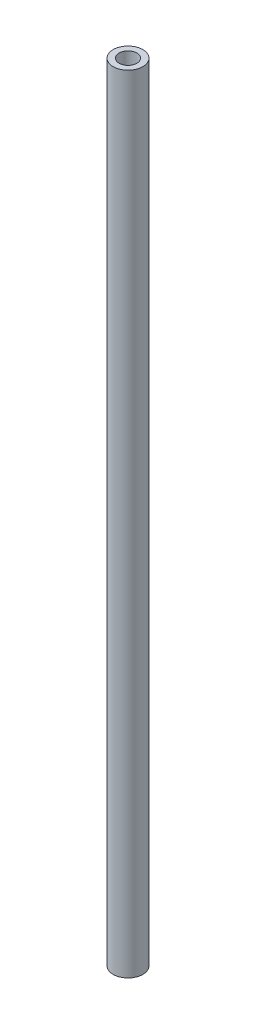
SolidWorks part; units mm, degrees
ref_plane "Front Plane" through (0, 0, 0) normal (0, 0, 1) x (1, 0, 0)
ref_plane "Top Plane" through (0, 0, 0) normal (0, 1, 0) x (1, 0, 0)
ref_plane "Right Plane" through (0, 0, 0) normal (1, 0, 0) x (0, 0, -1)
sketch "Sketch1" plane through (0, 0, 0) normal (0, 1, 0) x (1, 0, 0)
  circle A0 centre (0, 0) radius 2
  circle A1 centre (0, 0) radius 1.2
  dimension "D1" = 4
  dimension "D2" = 2.4
extrude "Boss-Extrude1" add sketch "Sketch1" along normal blind 106
